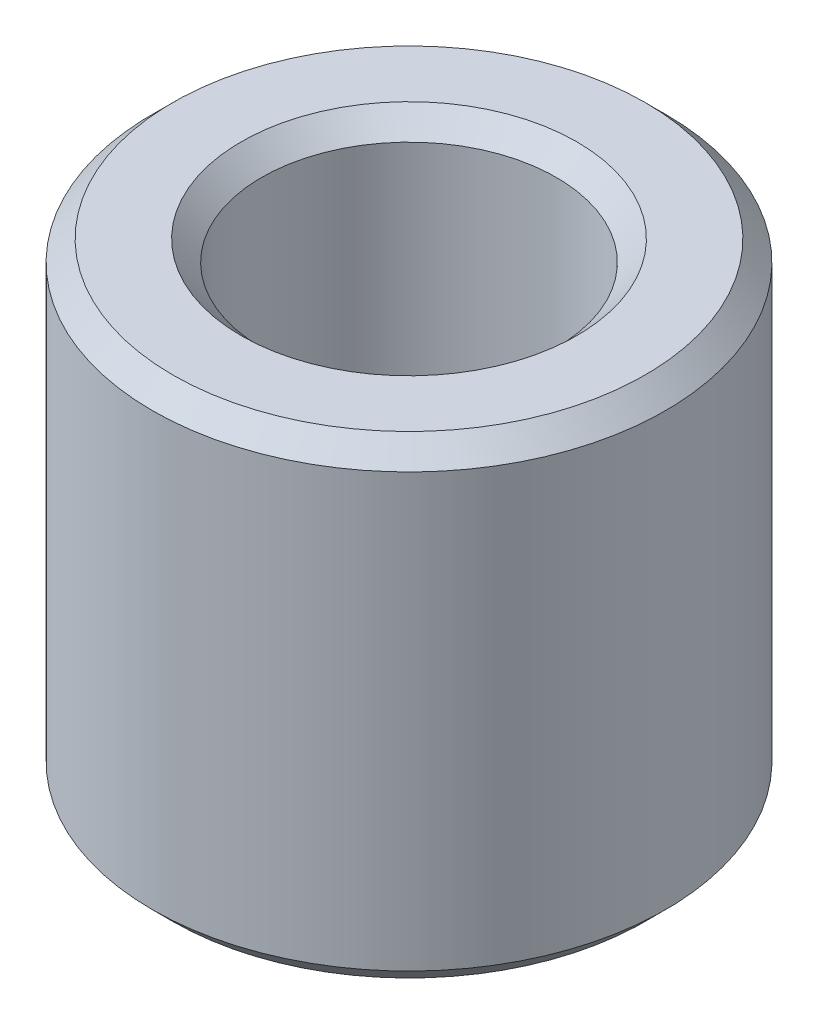
SolidWorks part; units mm, degrees
ref_plane "Front Plane" through (0, 0, 0) normal (0, 0, 1) x (1, 0, 0)
ref_plane "Top Plane" through (0, 0, 0) normal (0, 1, 0) x (1, 0, 0)
ref_plane "Right Plane" through (0, 0, 0) normal (1, 0, 0) x (0, 0, -1)
sketch "Sketch1" plane through (0, 0, 0) normal (0, 1, 0) x (1, 0, 0)
  circle A0 centre (0, 0) radius 47.5
  dimension "SLEEVE_OD" = 95
extrude "Boss-Extrude1" add sketch "Sketch1" along normal blind 87.6036
sketch "Sketch2" plane through (0, 0, 0) normal (0, 1, 0) x (1, 0, 0)
  circle A0 centre (0, 0) radius 27.2755
  dimension "BORE_D" = 54.5509
extrude "Cut-Extrude1" cut sketch "Sketch2" along normal through all
chamfer "Chamfer1" distance 3.7992 angle 45 4 edges at (0, 87.6036, 27.2755) (0, 0, 27.2755) (0, 0, 47.5) (0, 87.6036, 47.5)
